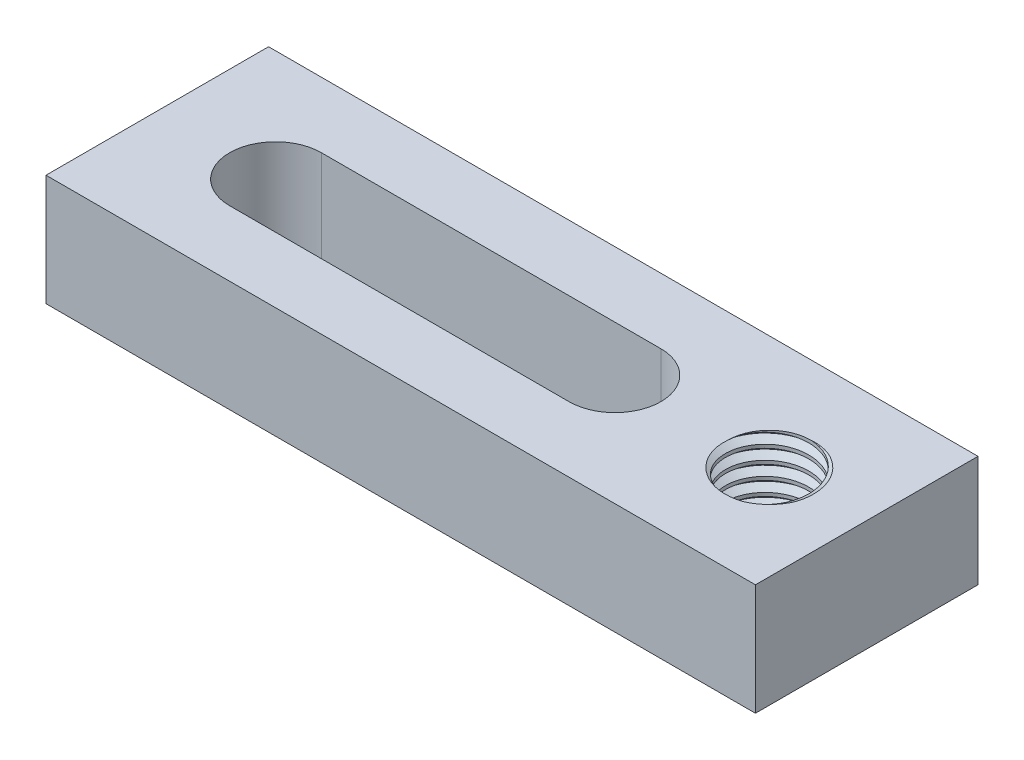
SolidWorks part; units mm, degrees
ref_plane "Alzado" through (0, 0, 0) normal (0, 0, 1) x (1, 0, 0)
ref_plane "Planta" through (0, 0, 0) normal (0, 1, 0) x (1, 0, 0)
ref_plane "Vista lateral" through (0, 0, 0) normal (1, 0, 0) x (0, 0, -1)
sketch "Croquis3" plane through (0, 0, 0) normal (0, 1, 0) x (1, 0, 0)
  line L1 (0, 0) -> (51, 0)
  line L2 (0, 0) -> (0, 16)
  line L3 (0, 16) -> (51, 16)
  line L4 (51, 0) -> (51, 16)
  dimension "D1" = 16
  dimension "D2" = 51
extrude "Saliente-Extruir1" add sketch "Croquis3" along normal blind 8 contours L1 L4 L3 L2
sketch "Croquis5" [suppressed] plane through (0, 6.2, 0) normal (0, 1, 0) x (1, 0, 0)
  line L0 (8.5, 8) -> (32.3, 8) construction
  line L1 (8.5, 11.3) -> (32.3, 11.3)
  line L2 (8.5, 4.7) -> (32.3, 4.7)
  line L3 (0, 0) -> (51, 0) construction
  line L4 (0, 0) -> (0, 16) construction
  line L6 (51, 0) -> (51, 16) construction
  arc A0 (8.5, 11.3) -> (8.5, 4.7) centre (8.5, 8) ccw
  arc A1 (32.3, 4.7) -> (32.3, 11.3) centre (32.3, 8) ccw
  circle A2 centre (45.5, 8) radius 3.3
  point P2 (20.4, 8)
  point P17 (5.2, 8)
  point P18 (35.6, 8)
  dimension "D3" = 6.6
  dimension "D1" = 8
  dimension "D2" = 5.5
  dimension "D4" = 8
  dimension "D5" = 8.5
  dimension "D6" = 6.6
  dimension "D7" = 30.4
sketch "Croquis15" plane through (0, 8, 0) normal (0, 1, 0) x (1, 0, 0)
  line L0 (8.5, 8) -> (32.9, 8) construction
  line L1 (8.5, 11.3) -> (32.9, 11.3)
  line L2 (8.5, 4.7) -> (32.9, 4.7)
  line L3 (0, 0) -> (51, 0) construction
  line L6 (0, 0) -> (0, 16) construction
  arc A0 (8.5, 11.3) -> (8.5, 4.7) centre (8.5, 8) ccw
  arc A1 (32.9, 4.7) -> (32.9, 11.3) centre (32.9, 8) ccw
  point P2 (20.7, 8)
  point P11 (0, 8)
  point P12 (5.2, 8)
  point P13 (36.2, 8)
  dimension "D1" = 8
  dimension "D2" = 8.5
  dimension "D3" = 6.6
  dimension "D4" = 31
extrude "Cortar-Extruir4" cut sketch "Croquis15" against normal through all contours L1 A1 L2 A0
sketch "Croquis32" plane through (0, 8, 0) normal (0, 1, 0) x (1, 0, 0)
  line L0 (51, 0) -> (51, 16) construction
  line L1 (0, 0) -> (51, 0) construction
  circle A0 centre (44, 8) radius 3
  dimension "D1" = 6
  dimension "D2" = 7
  dimension "D3" = 8
extrude "Cortar-Extruir6" cut sketch "Croquis32" against normal through all contours A0
thread "Rosca4" pitch 1 method cut profile "Perfil de rosca6" start angle 0, offset 5, length 0, pitch 1, diameter 6
ref_plane "Plano6" through (41, 13, -8) normal (0, 0, 1) x (-1, 0, 0)
sketch "Perfil de rosca6" plane through (41, 13, -8) normal (0, 0, 1) x (-1, 0, 0)
  line L0 (0, 0) -> (0, 1) construction
  line L1 (0, 0) -> (0.5413, 0.3125)
  line L2 (0.5413, 0.3125) -> (0.5413, 0.4375)
  line L3 (0.5413, 0.4375) -> (0, 0.75)
  line L4 (0.5413, 0.375) -> (0, 0.375) construction
  line L11 (0, 0) -> (0, 0.75)
  point P2 (0, 0)
  dimension "Pitch" = 1
  dimension "Profile_Angle" = 60
  dimension "Profile_Land" = 0.125
  dimension "Profile_Height" = 0.5413
